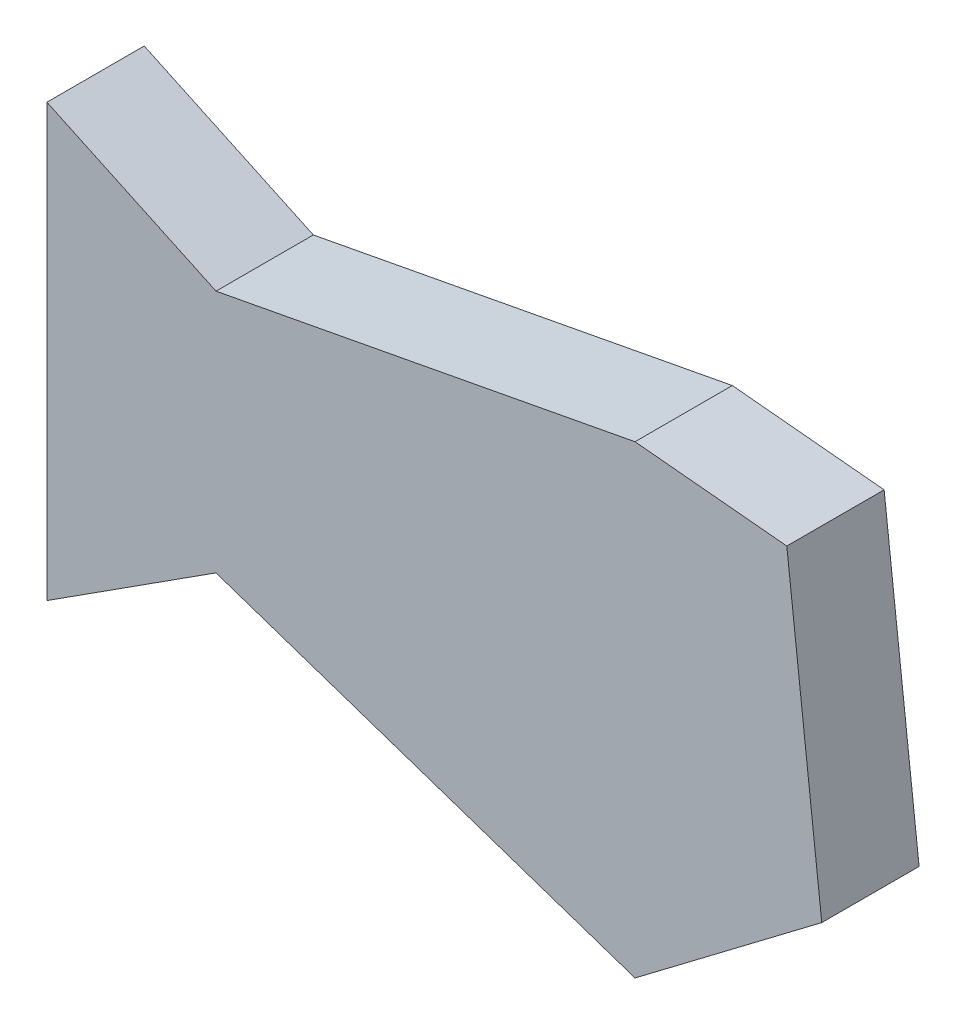
SolidWorks part; units mm, degrees
ref_plane "Спереди" through (0, 0, 0) normal (0, 0, 1) x (1, 0, 0)
ref_plane "Сверху" through (0, 0, 0) normal (0, 1, 0) x (1, 0, 0)
ref_plane "Справа" through (0, 0, 0) normal (1, 0, 0) x (0, 0, -1)
sketch "Эскиз1" plane through (0, 0, 0) normal (0, 0, 1) x (1, 0, 0)
  line L0 (-32.6763, 20.8765) -> (-32.6763, -23.4699)
  line L1 (-32.6763, -23.4699) -> (-15.3008, -12.3184)
  line L2 (-15.3008, -12.3184) -> (27.7489, -26.8413)
  line L3 (27.7489, -26.8413) -> (46.9398, -12.3184)
  line L4 (46.9398, -12.3184) -> (43.3468, 19.3953)
  line L5 (43.3468, 19.3953) -> (27.7489, 20.8765)
  line L6 (27.7489, 20.8765) -> (-15.3008, 12.7508)
  line L7 (-15.3008, 12.7508) -> (-32.6763, 20.8765)
extrude "Бобышка-Вытянуть1" add sketch "Эскиз1" along normal blind 10
